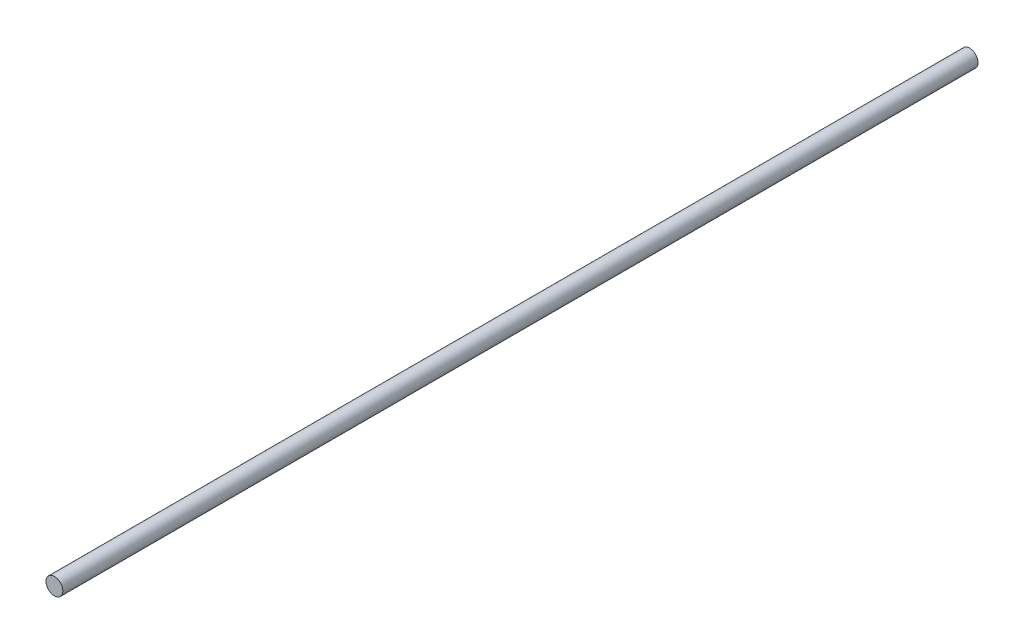
SolidWorks part; units mm, degrees
ref_plane "Front Plane" through (0, 0, 0) normal (0, 0, 1) x (1, 0, 0)
ref_plane "Top Plane" through (0, 0, 0) normal (0, 1, 0) x (1, 0, 0)
ref_plane "Right Plane" through (0, 0, 0) normal (1, 0, 0) x (0, 0, -1)
sketch "Sketch1" plane through (0, 0, 0) normal (0, 0, 1) x (1, 0, 0)
  circle A0 centre (0, 0) radius 4
extrude "Boss-Extrude1" add sketch "Sketch1" along normal blind 435
sketch "Sketch3" plane through (0, 0, 435) normal (0, 0, 1) x (1, 0, 0)
  circle A0 centre (0, 0) radius 4
curve "Helix/Spiral1" pitch 1.465 height 439.5 turns 300
sketch "Sketch4" plane through (0, 0, 0) normal (0, 1, 0) x (1, 0, 0)
  line L10 (-4, -378.8) -> (-4, -379.95)
  line L11 (-4, -379.95) -> (-2.75, -379.3625)
  line L12 (-4, -378.8) -> (-2.75, -379.3625)
sweep "Cut-Sweep1" [suppressed] cut profiles "Sketch4" path "Helix/Spiral1"
